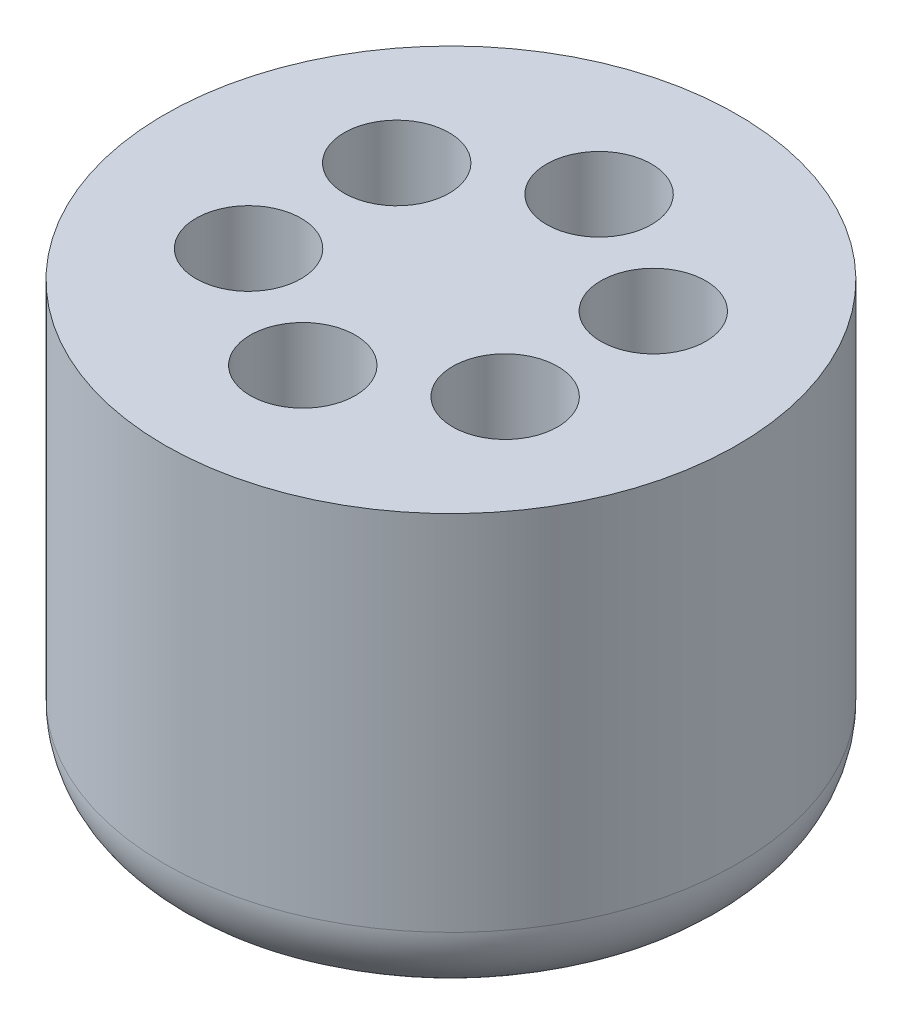
SolidWorks part; units mm, degrees
ref_plane "Front Plane" through (0, 0, 0) normal (0, 0, 1) x (1, 0, 0)
ref_plane "Top Plane" through (0, 0, 0) normal (0, 1, 0) x (1, 0, 0)
ref_plane "Right Plane" through (0, 0, 0) normal (1, 0, 0) x (0, 0, -1)
sketch "Sketch1" plane through (0, 0, 0) normal (0, 1, 0) x (1, 0, 0)
  circle A0 centre (0, 0) radius 30
extrude "Boss-Extrude1" add sketch "Sketch1" along normal blind 46
sketch "Sketch2" plane through (0, 46, 0) normal (0, 1, 0) x (1, 0, 0)
  circle A0 centre (0, 15.52) radius 5.5
  circle A2 centre (-13.4407, 7.76) radius 5.5
  circle A3 centre (-13.4407, -7.76) radius 5.5
  circle A4 centre (0, -15.52) radius 5.5
  circle A5 centre (13.4407, -7.76) radius 5.5
  circle A6 centre (13.4407, 7.76) radius 5.5
  dimension "D1" = 15.52
extrude "Cut-Extrude1" cut sketch "Sketch2" against normal blind 32
fillet "Fillet1" radius 8 1 edges at (0, 0, 30)
extrude "Cut-Extrude2" cut sketch "Sketch2<3>" against normal blind 35
sketch "Sketch2<3>" plane through (0, 46, 0) normal (0, 1, 0) x (1, 0, 0) same geometry as "Sketch2"
